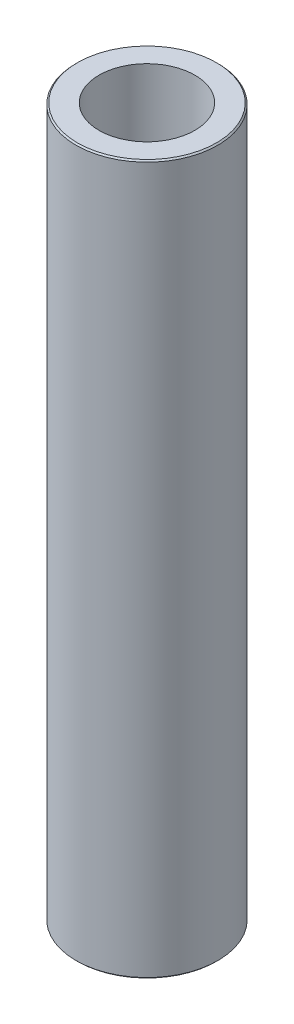
SolidWorks part; units mm, degrees
ref_plane "Front Plane" through (0, 0, 0) normal (0, 0, 1) x (1, 0, 0)
ref_plane "Top Plane" through (0, 0, 0) normal (0, 1, 0) x (1, 0, 0)
ref_plane "Right Plane" through (0, 0, 0) normal (1, 0, 0) x (0, 0, -1)
sketch "Sketch1" plane through (0, 0, 0) normal (0, 1, 0) x (1, 0, 0)
  circle A0 centre (0, 0) radius 60
  dimension "SHAFT_OD" = 120
extrude "Boss-Extrude1" add sketch "Sketch1" along normal blind 600
sketch "Sketch2" plane through (0, 0, 0) normal (0, 1, 0) x (1, 0, 0)
  circle A0 centre (0, 0) radius 40.5504
  dimension "BORE_D" = 81.1009
extrude "Cut-Extrude1" cut sketch "Sketch2" along normal through all
chamfer "Chamfer1" distance 1.1675 angle 45 2 edges at (0, 600, 60) (0, 0, 60)
